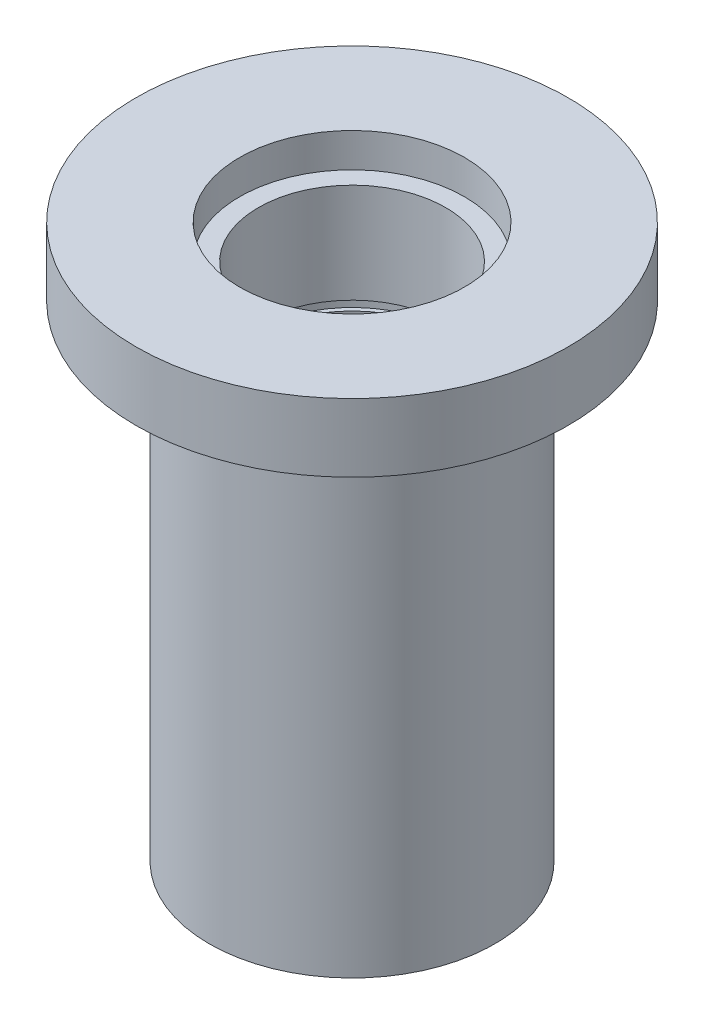
SolidWorks part; units mm, degrees
ref_plane "Front Plane" through (0, 0, 0) normal (0, 0, 1) x (1, 0, 0)
ref_plane "Top Plane" through (0, 0, 0) normal (0, 1, 0) x (1, 0, 0)
ref_plane "Right Plane" through (0, 0, 0) normal (1, 0, 0) x (0, 0, -1)
sketch "Sketch1" plane through (0, 0, 0) normal (0, 0, 1) x (1, 0, 0)
  line L0 (0, 0) -> (0, -122.9972) construction
  line L1 (25.3607, 0) -> (13.2, 0)
  line L2 (13.2, 0) -> (13.2, -4)
  line L3 (13.2, -4) -> (11, -4)
  line L4 (11, -4) -> (11, -15.7)
  line L9 (11, -65) -> (16.7743, -65)
  line L10 (16.7743, -65) -> (16.7743, -8)
  line L11 (16.7743, -8) -> (25.3607, -8)
  line L12 (25.3607, -8) -> (25.3607, 0)
  line L13 (11, -16.8) -> (11, -31.2)
  line L14 (11, -15.7) -> (11.5, -15.7)
  line L16 (11, -16.8) -> (11.5, -16.8)
  line L17 (11.5, -15.7) -> (11.5, -16.8)
  line L18 (11, -31.2) -> (11.5, -31.2)
  line L20 (11, -32.3) -> (11.5, -32.3)
  line L21 (11.5, -31.2) -> (11.5, -32.3)
  line L22 (11, -32.3) -> (11, -65)
  point P19 (16.7743, -6.9871)
  point P20 (11.5, -19.4497)
  point P21 (11.5, -25.6709)
  point P22 (16.7171, -6.4788)
  point P23 (11.5, -36.2464)
  dimension "D1" = 22
  dimension "D2" = 26.4
  dimension "D3" = 4
  dimension "D4" = 15.7
  dimension "D5" = 1.1
  dimension "D6" = 23
  dimension "D7" = 32.3
  dimension "D8" = 65
  dimension "D9" = 8
revolve "Revolve1" add sketch "Sketch1" angle 360 about L0
